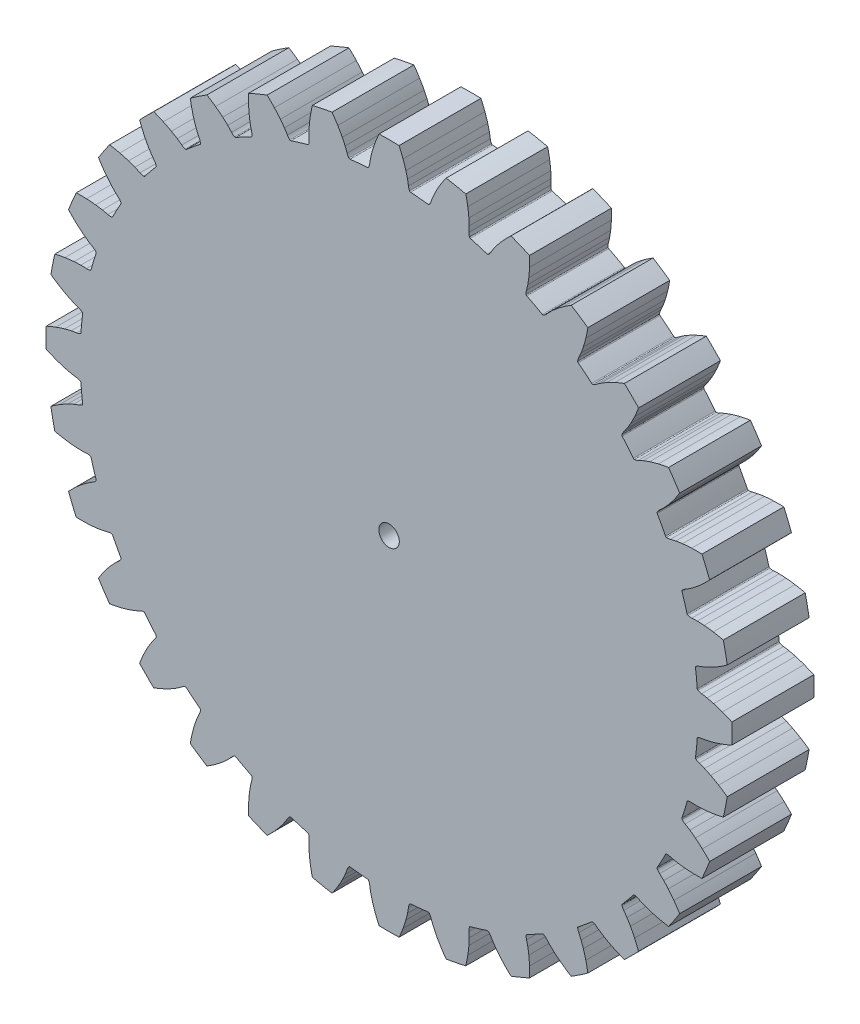
SolidWorks part; units mm, degrees
ref_plane "Front Plane" through (0, 0, 0) normal (0, 0, 1) x (1, 0, 0)
ref_plane "Top Plane" through (0, 0, 0) normal (0, 1, 0) x (1, 0, 0)
ref_plane "Right Plane" through (0, 0, 0) normal (1, 0, 0) x (0, 0, -1)
sketch "Model" plane through (0, 0, 0) normal (0, 0, 1) x (1, 0, 0)
  arc A1 (47.6887, -4.6969) -> (47.803, -3.3385) centre (0, 0) ccw
  arc A2 (47.9144, -3.1714) -> (47.803, -3.3385) centre (48.0052, -3.3526) ccw
  arc A3 (48.4758, -3.0015) -> (47.9144, -3.1714) centre (48.6888, -4.7173) ccw
  arc A4 (48.4758, -3.0015) -> (49.3301, -2.859) centre (47.1969, 7.2969) ccw
  arc A5 (49.3301, -2.859) -> (50.3502, -2.6078) centre (46.1914, 12.0843) ccw
  arc A6 (50.3502, -2.6078) -> (51.6994, -2.1663) centre (45.5635, 14.3022) ccw
  arc A7 (51.6994, -2.1663) -> (53.1817, -1.5528) centre (43.8651, 18.8607) ccw
  arc A8 (53.1817, -1.5528) -> (53.1817, 1.5528) centre (0, 0) ccw
  arc A9 (53.1817, 1.5528) -> (51.6994, 2.1663) centre (43.8651, -18.8607) ccw
  arc A10 (51.6994, 2.1663) -> (50.3502, 2.6078) centre (45.5635, -14.3022) ccw
  arc A11 (50.3502, 2.6078) -> (49.3301, 2.859) centre (46.1914, -12.0843) ccw
  arc A12 (49.3301, 2.859) -> (48.4758, 3.0015) centre (47.1969, -7.2969) ccw
  arc A13 (47.9144, 3.1714) -> (48.4758, 3.0015) centre (48.6888, 4.7173) ccw
  arc A14 (47.803, 3.3385) -> (47.9144, 3.1714) centre (48.0052, 3.3526) ccw
  arc A15 (47.803, 3.3385) -> (47.5358, 6.0515) centre (0, 0) ccw
  arc A16 (47.6124, 6.2371) -> (47.5358, 6.0515) centre (47.7368, 6.0771) ccw
  arc A17 (48.1299, 6.5133) -> (47.6124, 6.2371) centre (48.6736, 4.872) ccw
  arc A18 (48.1299, 6.5133) -> (48.94, 6.8198) centre (44.8665, 16.3643) ccw
  arc A19 (48.94, 6.8198) -> (49.8915, 7.2652) centre (42.9463, 20.8636) ccw
  arc A20 (49.8915, 7.2652) -> (51.1287, 7.9614) centre (41.8978, 22.9164) ccw
  arc A21 (51.1287, 7.9614) -> (52.4627, 8.8522) centre (39.3427, 27.056) ccw
  arc A22 (52.4627, 8.8522) -> (51.8568, 11.8982) centre (0, 0) ccw
  arc A23 (51.8568, 11.8982) -> (50.2834, 12.2107) centre (46.7018, -9.9407) ccw
  arc A24 (50.2834, 12.2107) -> (48.874, 12.3805) centre (47.4783, -5.1384) ccw
  arc A25 (48.874, 12.3805) -> (47.8244, 12.4279) centre (47.6613, -2.8406) ccw
  arc A26 (47.8244, 12.4279) -> (46.9587, 12.401) centre (47.7136, 2.051) ccw
  arc A27 (46.375, 12.4581) -> (46.9587, 12.401) centre (46.833, 14.1254) ccw
  arc A28 (46.2332, 12.6003) -> (46.375, 12.4581) centre (46.4287, 12.6536) ccw
  arc A29 (46.2332, 12.6003) -> (45.4418, 15.209) centre (0, 0) ccw
  arc A30 (45.4808, 15.406) -> (45.4418, 15.209) centre (45.634, 15.2733) ccw
  arc A31 (45.9344, 15.7779) -> (45.4808, 15.406) centre (46.7879, 14.2741) ccw
  arc A32 (45.9344, 15.7779) -> (46.6691, 16.2364) centre (40.8119, 24.8029) ccw
  arc A33 (46.6691, 16.2364) -> (47.5155, 16.8589) centre (38.0508, 28.8411) ccw
  arc A34 (47.5155, 16.8589) -> (48.5931, 17.7832) centre (36.622, 30.6499) ccw
  arc A35 (48.5931, 17.7832) -> (49.7277, 18.9171) centre (33.3084, 34.2115) ccw
  arc A36 (49.7277, 18.9171) -> (48.5392, 21.7864) centre (0, 0) ccw
  arc A37 (48.5392, 21.7864) -> (46.9351, 21.7859) centre (47.7438, -0.6386) ccw
  arc A38 (46.9351, 21.7859) -> (45.5196, 21.6775) centre (47.5684, 4.2229) ccw
  arc A39 (45.5196, 21.6775) -> (44.481, 21.5192) centre (47.2997, 6.5122) ccw
  arc A40 (44.481, 21.5192) -> (43.6371, 21.3239) centre (46.3967, 11.3201) ccw
  arc A41 (43.0535, 21.2661) -> (43.6371, 21.3239) centre (43.1774, 22.9907) ccw
  arc A42 (42.8866, 21.3778) -> (43.0535, 21.2661) centre (43.068, 21.4682) ccw
  arc A43 (42.8866, 21.3778) -> (41.6015, 23.782) centre (0, 0) ccw
  arc A44 (41.6013, 23.9828) -> (41.6015, 23.782) centre (41.7775, 23.8826) ccw
  arc A45 (41.9737, 24.436) -> (41.6013, 23.9828) centre (43.1041, 23.1277) ccw
  arc A46 (41.9737, 24.436) -> (42.6048, 25.0292) centre (35.1889, 32.2883) ccw
  arc A47 (42.6048, 25.0292) -> (43.3135, 25.8048) centre (31.693, 35.7103) ccw
  arc A48 (43.3135, 25.8048) -> (44.19, 26.9215) centre (29.9388, 37.2056) ccw
  arc A49 (44.19, 26.9215) -> (45.0816, 28.255) centre (25.994, 40.0523) ccw
  arc A50 (45.0816, 28.255) -> (43.3562, 30.8373) centre (0, 0) ccw
  arc A51 (43.3562, 30.8373) -> (41.783, 30.5239) centre (46.951, 8.688) ccw
  arc A52 (41.783, 30.5239) -> (40.4159, 30.1414) centre (45.8306, 13.4219) ccw
  arc A53 (40.4159, 30.1414) -> (39.4281, 29.7835) centre (45.1204, 15.6148) ccw
  arc A54 (39.4281, 29.7835) -> (38.6386, 29.4273) centre (43.2967, 20.1541) ccw
  arc A55 (38.0774, 29.2568) -> (38.6386, 29.4273) centre (37.8625, 30.9724) ccw
  arc A56 (37.892, 29.3338) -> (38.0774, 29.2568) centre (38.0522, 29.4579) ccw
  arc A57 (37.892, 29.3338) -> (36.1625, 31.4411) centre (0, 0) ccw
  arc A58 (36.1231, 31.638) -> (36.1625, 31.4411) centre (36.3154, 31.5741) ccw
  arc A59 (36.3999, 32.1552) -> (36.1231, 31.638) centre (37.7639, 31.0925) ccw
  arc A60 (36.3999, 32.1552) -> (36.9032, 32.86) centre (28.2136, 38.5329) ccw
  arc A61 (36.9032, 32.86) -> (37.447, 33.759) centre (24.1173, 41.2071) ccw
  arc A62 (37.447, 33.759) -> (38.0888, 35.0253) centre (22.1051, 42.3315) ccw
  arc A63 (38.0888, 35.0253) -> (38.7031, 36.5071) centre (17.6808, 44.3539) ccw
  arc A64 (38.7031, 36.5071) -> (36.5071, 38.7031) centre (0, 0) ccw
  arc A65 (36.5071, 38.7031) -> (35.0253, 38.0888) centre (44.3539, 17.6808) ccw
  arc A66 (35.0253, 38.0888) -> (33.759, 37.447) centre (42.3315, 22.1051) ccw
  arc A67 (33.759, 37.447) -> (32.86, 36.9032) centre (41.2071, 24.1173) ccw
  arc A68 (32.86, 36.9032) -> (32.1552, 36.3999) centre (38.5329, 28.2136) ccw
  arc A69 (31.638, 36.1231) -> (32.1552, 36.3999) centre (31.0925, 37.7639) ccw
  arc A70 (31.4411, 36.1625) -> (31.638, 36.1231) centre (31.5741, 36.3154) ccw
  arc A71 (31.4411, 36.1625) -> (29.3338, 37.892) centre (0, 0) ccw
  arc A72 (29.2568, 38.0774) -> (29.3338, 37.892) centre (29.4579, 38.0522) ccw
  arc A73 (29.4273, 38.6386) -> (29.2568, 38.0774) centre (30.9724, 37.8625) ccw
  arc A74 (29.4273, 38.6386) -> (29.7835, 39.4281) centre (20.1541, 43.2967) ccw
  arc A75 (29.7835, 39.4281) -> (30.1414, 40.4159) centre (15.6148, 45.1204) ccw
  arc A76 (30.1414, 40.4159) -> (30.5239, 41.783) centre (13.4219, 45.8306) ccw
  arc A77 (30.5239, 41.783) -> (30.8373, 43.3562) centre (8.688, 46.951) ccw
  arc A78 (30.8373, 43.3562) -> (28.255, 45.0816) centre (0, 0) ccw
  arc A79 (28.255, 45.0816) -> (26.9215, 44.19) centre (40.0523, 25.994) ccw
  arc A80 (26.9215, 44.19) -> (25.8048, 43.3135) centre (37.2056, 29.9388) ccw
  arc A81 (25.8048, 43.3135) -> (25.0292, 42.6048) centre (35.7103, 31.693) ccw
  arc A82 (25.0292, 42.6048) -> (24.436, 41.9737) centre (32.2883, 35.1889) ccw
  arc A83 (23.9828, 41.6013) -> (24.436, 41.9737) centre (23.1277, 43.1041) ccw
  arc A84 (23.782, 41.6015) -> (23.9828, 41.6013) centre (23.8826, 41.7775) ccw
  arc A85 (23.782, 41.6015) -> (21.3778, 42.8866) centre (0, 0) ccw
  arc A86 (21.2661, 43.0535) -> (21.3778, 42.8866) centre (21.4682, 43.068) ccw
  arc A87 (21.3239, 43.6371) -> (21.2661, 43.0535) centre (22.9907, 43.1774) ccw
  arc A88 (21.3239, 43.6371) -> (21.5192, 44.481) centre (11.3201, 46.3967) ccw
  arc A89 (21.5192, 44.481) -> (21.6775, 45.5196) centre (6.5122, 47.2997) ccw
  arc A90 (21.6775, 45.5196) -> (21.7859, 46.9351) centre (4.2229, 47.5684) ccw
  arc A91 (21.7859, 46.9351) -> (21.7864, 48.5392) centre (-0.6386, 47.7438) ccw
  arc A92 (21.7864, 48.5392) -> (18.9171, 49.7277) centre (0, 0) ccw
  arc A93 (18.9171, 49.7277) -> (17.7832, 48.5931) centre (34.2115, 33.3084) ccw
  arc A94 (17.7832, 48.5931) -> (16.8589, 47.5155) centre (30.6499, 36.622) ccw
  arc A95 (16.8589, 47.5155) -> (16.2364, 46.6691) centre (28.8411, 38.0508) ccw
  arc A96 (16.2364, 46.6691) -> (15.7779, 45.9344) centre (24.8029, 40.8119) ccw
  arc A97 (15.406, 45.4808) -> (15.7779, 45.9344) centre (14.2741, 46.7879) ccw
  arc A98 (15.209, 45.4418) -> (15.406, 45.4808) centre (15.2733, 45.634) ccw
  arc A99 (15.209, 45.4418) -> (12.6003, 46.2332) centre (0, 0) ccw
  arc A100 (12.4581, 46.375) -> (12.6003, 46.2332) centre (12.6536, 46.4287) ccw
  arc A101 (12.401, 46.9587) -> (12.4581, 46.375) centre (14.1254, 46.833) ccw
  arc A102 (12.401, 46.9587) -> (12.4279, 47.8244) centre (2.051, 47.7136) ccw
  arc A103 (12.4279, 47.8244) -> (12.3805, 48.874) centre (-2.8406, 47.6613) ccw
  arc A104 (12.3805, 48.874) -> (12.2107, 50.2834) centre (-5.1384, 47.4783) ccw
  arc A105 (12.2107, 50.2834) -> (11.8982, 51.8568) centre (-9.9407, 46.7018) ccw
  arc A106 (11.8982, 51.8568) -> (8.8522, 52.4627) centre (0, 0) ccw
  arc A107 (8.8522, 52.4627) -> (7.9614, 51.1287) centre (27.056, 39.3427) ccw
  arc A108 (7.9614, 51.1287) -> (7.2652, 49.8915) centre (22.9164, 41.8978) ccw
  arc A109 (7.2652, 49.8915) -> (6.8198, 48.94) centre (20.8636, 42.9463) ccw
  arc A110 (6.8198, 48.94) -> (6.5133, 48.1299) centre (16.3643, 44.8665) ccw
  arc A111 (6.2371, 47.6124) -> (6.5133, 48.1299) centre (4.872, 48.6736) ccw
  arc A112 (6.0515, 47.5358) -> (6.2371, 47.6124) centre (6.0771, 47.7368) ccw
  arc A113 (6.0515, 47.5358) -> (3.3385, 47.803) centre (0, 0) ccw
  arc A114 (3.1714, 47.9144) -> (3.3385, 47.803) centre (3.3526, 48.0052) ccw
  arc A115 (3.0015, 48.4758) -> (3.1714, 47.9144) centre (4.7173, 48.6888) ccw
  arc A116 (3.0015, 48.4758) -> (2.859, 49.3301) centre (-7.2969, 47.1969) ccw
  arc A117 (2.859, 49.3301) -> (2.6078, 50.3502) centre (-12.0843, 46.1914) ccw
  arc A118 (2.6078, 50.3502) -> (2.1663, 51.6994) centre (-14.3022, 45.5635) ccw
  arc A119 (2.1663, 51.6994) -> (1.5528, 53.1817) centre (-18.8607, 43.8651) ccw
  arc A120 (1.5528, 53.1817) -> (-1.5528, 53.1817) centre (0, 0) ccw
  arc A121 (-1.5528, 53.1817) -> (-2.1663, 51.6994) centre (18.8607, 43.8651) ccw
  arc A122 (-2.1663, 51.6994) -> (-2.6078, 50.3502) centre (14.3022, 45.5635) ccw
  arc A123 (-2.6078, 50.3502) -> (-2.859, 49.3301) centre (12.0843, 46.1914) ccw
  arc A124 (-2.859, 49.3301) -> (-3.0015, 48.4758) centre (7.2969, 47.1969) ccw
  arc A125 (-3.1714, 47.9144) -> (-3.0015, 48.4758) centre (-4.7173, 48.6888) ccw
  arc A126 (-3.3385, 47.803) -> (-3.1714, 47.9144) centre (-3.3526, 48.0052) ccw
  arc A127 (-3.3385, 47.803) -> (-6.0515, 47.5358) centre (0, 0) ccw
  arc A128 (-6.2371, 47.6124) -> (-6.0515, 47.5358) centre (-6.0771, 47.7368) ccw
  arc A129 (-6.5133, 48.1299) -> (-6.2371, 47.6124) centre (-4.872, 48.6736) ccw
  arc A130 (-6.5133, 48.1299) -> (-6.8198, 48.94) centre (-16.3643, 44.8665) ccw
  arc A131 (-6.8198, 48.94) -> (-7.2652, 49.8915) centre (-20.8636, 42.9463) ccw
  arc A132 (-7.2652, 49.8915) -> (-7.9614, 51.1287) centre (-22.9164, 41.8978) ccw
  arc A133 (-7.9614, 51.1287) -> (-8.8522, 52.4627) centre (-27.056, 39.3427) ccw
  arc A134 (-8.8522, 52.4627) -> (-11.8982, 51.8568) centre (0, 0) ccw
  arc A135 (-11.8982, 51.8568) -> (-12.2107, 50.2834) centre (9.9407, 46.7018) ccw
  arc A136 (-12.2107, 50.2834) -> (-12.3805, 48.874) centre (5.1384, 47.4783) ccw
  arc A137 (-12.3805, 48.874) -> (-12.4279, 47.8244) centre (2.8406, 47.6613) ccw
  arc A138 (-12.4279, 47.8244) -> (-12.401, 46.9587) centre (-2.051, 47.7136) ccw
  arc A139 (-12.4581, 46.375) -> (-12.401, 46.9587) centre (-14.1254, 46.833) ccw
  arc A140 (-12.6003, 46.2332) -> (-12.4581, 46.375) centre (-12.6536, 46.4287) ccw
  arc A141 (-12.6003, 46.2332) -> (-15.209, 45.4418) centre (0, 0) ccw
  arc A142 (-15.406, 45.4808) -> (-15.209, 45.4418) centre (-15.2733, 45.634) ccw
  arc A143 (-15.7779, 45.9344) -> (-15.406, 45.4808) centre (-14.2741, 46.7879) ccw
  arc A144 (-15.7779, 45.9344) -> (-16.2364, 46.6691) centre (-24.8029, 40.8119) ccw
  arc A145 (-16.2364, 46.6691) -> (-16.8589, 47.5155) centre (-28.8411, 38.0508) ccw
  arc A146 (-16.8589, 47.5155) -> (-17.7832, 48.5931) centre (-30.6499, 36.622) ccw
  arc A147 (-17.7832, 48.5931) -> (-18.9171, 49.7277) centre (-34.2115, 33.3084) ccw
  arc A148 (-18.9171, 49.7277) -> (-21.7864, 48.5392) centre (0, 0) ccw
  arc A149 (-21.7864, 48.5392) -> (-21.7859, 46.9351) centre (0.6386, 47.7438) ccw
  arc A150 (-21.7859, 46.9351) -> (-21.6775, 45.5196) centre (-4.2229, 47.5684) ccw
  arc A151 (-21.6775, 45.5196) -> (-21.5192, 44.481) centre (-6.5122, 47.2997) ccw
  arc A152 (-21.5192, 44.481) -> (-21.3239, 43.6371) centre (-11.3201, 46.3967) ccw
  arc A153 (-21.2661, 43.0535) -> (-21.3239, 43.6371) centre (-22.9907, 43.1774) ccw
  arc A154 (-21.3778, 42.8866) -> (-21.2661, 43.0535) centre (-21.4682, 43.068) ccw
  arc A155 (-21.3778, 42.8866) -> (-23.782, 41.6015) centre (0, 0) ccw
  arc A156 (-23.9828, 41.6013) -> (-23.782, 41.6015) centre (-23.8826, 41.7775) ccw
  arc A157 (-24.436, 41.9737) -> (-23.9828, 41.6013) centre (-23.1277, 43.1041) ccw
  arc A158 (-24.436, 41.9737) -> (-25.0292, 42.6048) centre (-32.2883, 35.1889) ccw
  arc A159 (-25.0292, 42.6048) -> (-25.8048, 43.3135) centre (-35.7103, 31.693) ccw
  arc A160 (-25.8048, 43.3135) -> (-26.9215, 44.19) centre (-37.2056, 29.9388) ccw
  arc A161 (-26.9215, 44.19) -> (-28.255, 45.0816) centre (-40.0523, 25.994) ccw
  arc A162 (-28.255, 45.0816) -> (-30.8373, 43.3562) centre (0, 0) ccw
  arc A163 (-30.8373, 43.3562) -> (-30.5239, 41.783) centre (-8.688, 46.951) ccw
  arc A164 (-30.5239, 41.783) -> (-30.1414, 40.4159) centre (-13.4219, 45.8306) ccw
  arc A165 (-30.1414, 40.4159) -> (-29.7835, 39.4281) centre (-15.6148, 45.1204) ccw
  arc A166 (-29.7835, 39.4281) -> (-29.4273, 38.6386) centre (-20.1541, 43.2967) ccw
  arc A167 (-29.2568, 38.0774) -> (-29.4273, 38.6386) centre (-30.9724, 37.8625) ccw
  arc A168 (-29.3338, 37.892) -> (-29.2568, 38.0774) centre (-29.4579, 38.0522) ccw
  arc A169 (-29.3338, 37.892) -> (-31.4411, 36.1625) centre (0, 0) ccw
  arc A170 (-31.638, 36.1231) -> (-31.4411, 36.1625) centre (-31.5741, 36.3154) ccw
  arc A171 (-32.1552, 36.3999) -> (-31.638, 36.1231) centre (-31.0925, 37.7639) ccw
  arc A172 (-32.1552, 36.3999) -> (-32.86, 36.9032) centre (-38.5329, 28.2136) ccw
  arc A173 (-32.86, 36.9032) -> (-33.759, 37.447) centre (-41.2071, 24.1173) ccw
  arc A174 (-33.759, 37.447) -> (-35.0253, 38.0888) centre (-42.3315, 22.1051) ccw
  arc A175 (-35.0253, 38.0888) -> (-36.5071, 38.7031) centre (-44.3539, 17.6808) ccw
  arc A176 (-36.5071, 38.7031) -> (-38.7031, 36.5071) centre (0, 0) ccw
  arc A177 (-38.7031, 36.5071) -> (-38.0888, 35.0253) centre (-17.6808, 44.3539) ccw
  arc A178 (-38.0888, 35.0253) -> (-37.447, 33.759) centre (-22.1051, 42.3315) ccw
  arc A179 (-37.447, 33.759) -> (-36.9032, 32.86) centre (-24.1173, 41.2071) ccw
  arc A180 (-36.9032, 32.86) -> (-36.3999, 32.1552) centre (-28.2136, 38.5329) ccw
  arc A181 (-36.1231, 31.638) -> (-36.3999, 32.1552) centre (-37.7639, 31.0925) ccw
  arc A182 (-36.1625, 31.4411) -> (-36.1231, 31.638) centre (-36.3154, 31.5741) ccw
  arc A183 (-36.1625, 31.4411) -> (-37.892, 29.3338) centre (0, 0) ccw
  arc A184 (-38.0774, 29.2568) -> (-37.892, 29.3338) centre (-38.0522, 29.4579) ccw
  arc A185 (-38.6386, 29.4273) -> (-38.0774, 29.2568) centre (-37.8625, 30.9724) ccw
  arc A186 (-38.6386, 29.4273) -> (-39.4281, 29.7835) centre (-43.2967, 20.1541) ccw
  arc A187 (-39.4281, 29.7835) -> (-40.4159, 30.1414) centre (-45.1204, 15.6148) ccw
  arc A188 (-40.4159, 30.1414) -> (-41.783, 30.5239) centre (-45.8306, 13.4219) ccw
  arc A189 (-41.783, 30.5239) -> (-43.3562, 30.8373) centre (-46.951, 8.688) ccw
  arc A190 (-43.3562, 30.8373) -> (-45.0816, 28.255) centre (0, 0) ccw
  arc A191 (-45.0816, 28.255) -> (-44.19, 26.9215) centre (-25.994, 40.0523) ccw
  arc A192 (-44.19, 26.9215) -> (-43.3135, 25.8048) centre (-29.9388, 37.2056) ccw
  arc A193 (-43.3135, 25.8048) -> (-42.6048, 25.0292) centre (-31.693, 35.7103) ccw
  arc A194 (-42.6048, 25.0292) -> (-41.9737, 24.436) centre (-35.1889, 32.2883) ccw
  arc A195 (-41.6013, 23.9828) -> (-41.9737, 24.436) centre (-43.1041, 23.1277) ccw
  arc A196 (-41.6015, 23.782) -> (-41.6013, 23.9828) centre (-41.7775, 23.8826) ccw
  arc A197 (-41.6015, 23.782) -> (-42.8866, 21.3778) centre (0, 0) ccw
  arc A198 (-43.0535, 21.2661) -> (-42.8866, 21.3778) centre (-43.068, 21.4682) ccw
  arc A199 (-43.6371, 21.3239) -> (-43.0535, 21.2661) centre (-43.1774, 22.9907) ccw
  arc A200 (-43.6371, 21.3239) -> (-44.481, 21.5192) centre (-46.3967, 11.3201) ccw
  arc A201 (-44.481, 21.5192) -> (-45.5196, 21.6775) centre (-47.2997, 6.5122) ccw
  arc A202 (-45.5196, 21.6775) -> (-46.9351, 21.7859) centre (-47.5684, 4.2229) ccw
  arc A203 (-46.9351, 21.7859) -> (-48.5392, 21.7864) centre (-47.7438, -0.6386) ccw
  arc A204 (-48.5392, 21.7864) -> (-49.7277, 18.9171) centre (0, 0) ccw
  arc A205 (-49.7277, 18.9171) -> (-48.5931, 17.7832) centre (-33.3084, 34.2115) ccw
  arc A206 (-48.5931, 17.7832) -> (-47.5155, 16.8589) centre (-36.622, 30.6499) ccw
  arc A207 (-47.5155, 16.8589) -> (-46.6691, 16.2364) centre (-38.0508, 28.8411) ccw
  arc A208 (-46.6691, 16.2364) -> (-45.9344, 15.7779) centre (-40.8119, 24.8029) ccw
  arc A209 (-45.4808, 15.406) -> (-45.9344, 15.7779) centre (-46.7879, 14.2741) ccw
  arc A210 (-45.4418, 15.209) -> (-45.4808, 15.406) centre (-45.634, 15.2733) ccw
  arc A211 (-45.4418, 15.209) -> (-46.2332, 12.6003) centre (0, 0) ccw
  arc A212 (-46.375, 12.4581) -> (-46.2332, 12.6003) centre (-46.4287, 12.6536) ccw
  arc A213 (-46.9587, 12.401) -> (-46.375, 12.4581) centre (-46.833, 14.1254) ccw
  arc A214 (-46.9587, 12.401) -> (-47.8244, 12.4279) centre (-47.7136, 2.051) ccw
  arc A215 (-47.8244, 12.4279) -> (-48.874, 12.3805) centre (-47.6613, -2.8406) ccw
  arc A216 (-48.874, 12.3805) -> (-50.2834, 12.2107) centre (-47.4783, -5.1384) ccw
  arc A217 (-50.2834, 12.2107) -> (-51.8568, 11.8982) centre (-46.7018, -9.9407) ccw
  arc A218 (-51.8568, 11.8982) -> (-52.4627, 8.8522) centre (0, 0) ccw
  arc A219 (-52.4627, 8.8522) -> (-51.1287, 7.9614) centre (-39.3427, 27.056) ccw
  arc A220 (-51.1287, 7.9614) -> (-49.8915, 7.2652) centre (-41.8978, 22.9164) ccw
  arc A221 (-49.8915, 7.2652) -> (-48.94, 6.8198) centre (-42.9463, 20.8636) ccw
  arc A222 (-48.94, 6.8198) -> (-48.1299, 6.5133) centre (-44.8665, 16.3643) ccw
  arc A223 (-47.6124, 6.2371) -> (-48.1299, 6.5133) centre (-48.6736, 4.872) ccw
  arc A224 (-47.5358, 6.0515) -> (-47.6124, 6.2371) centre (-47.7368, 6.0771) ccw
  arc A225 (-47.5358, 6.0515) -> (-47.803, 3.3385) centre (0, 0) ccw
  arc A226 (-47.9144, 3.1714) -> (-47.803, 3.3385) centre (-48.0052, 3.3526) ccw
  arc A227 (-48.4758, 3.0015) -> (-47.9144, 3.1714) centre (-48.6888, 4.7173) ccw
  arc A228 (-48.4758, 3.0015) -> (-49.3301, 2.859) centre (-47.1969, -7.2969) ccw
  arc A229 (-49.3301, 2.859) -> (-50.3502, 2.6078) centre (-46.1914, -12.0843) ccw
  arc A230 (-50.3502, 2.6078) -> (-51.6994, 2.1663) centre (-45.5635, -14.3022) ccw
  arc A231 (-51.6994, 2.1663) -> (-53.1817, 1.5528) centre (-43.8651, -18.8607) ccw
  arc A232 (-53.1817, 1.5528) -> (-53.1817, -1.5528) centre (0, 0) ccw
  arc A233 (-53.1817, -1.5528) -> (-51.6994, -2.1663) centre (-43.8651, 18.8607) ccw
  arc A234 (-51.6994, -2.1663) -> (-50.3502, -2.6078) centre (-45.5635, 14.3022) ccw
  arc A235 (-50.3502, -2.6078) -> (-49.3301, -2.859) centre (-46.1914, 12.0843) ccw
  arc A236 (-49.3301, -2.859) -> (-48.4758, -3.0015) centre (-47.1969, 7.2969) ccw
  arc A237 (-47.9144, -3.1714) -> (-48.4758, -3.0015) centre (-48.6888, -4.7173) ccw
  arc A238 (-47.803, -3.3385) -> (-47.9144, -3.1714) centre (-48.0052, -3.3526) ccw
  arc A239 (-47.803, -3.3385) -> (-47.5358, -6.0515) centre (0, 0) ccw
  arc A240 (-47.6124, -6.2371) -> (-47.5358, -6.0515) centre (-47.7368, -6.0771) ccw
  arc A241 (-48.1299, -6.5133) -> (-47.6124, -6.2371) centre (-48.6736, -4.872) ccw
  arc A242 (-48.1299, -6.5133) -> (-48.94, -6.8198) centre (-44.8665, -16.3643) ccw
  arc A243 (-48.94, -6.8198) -> (-49.8915, -7.2652) centre (-42.9463, -20.8636) ccw
  arc A244 (-49.8915, -7.2652) -> (-51.1287, -7.9614) centre (-41.8978, -22.9164) ccw
  arc A245 (-51.1287, -7.9614) -> (-52.4627, -8.8522) centre (-39.3427, -27.056) ccw
  arc A246 (-52.4627, -8.8522) -> (-51.8568, -11.8982) centre (0, 0) ccw
  arc A247 (-51.8568, -11.8982) -> (-50.2834, -12.2107) centre (-46.7018, 9.9407) ccw
  arc A248 (-50.2834, -12.2107) -> (-48.874, -12.3805) centre (-47.4783, 5.1384) ccw
  arc A249 (-48.874, -12.3805) -> (-47.8244, -12.4279) centre (-47.6613, 2.8406) ccw
  arc A250 (-47.8244, -12.4279) -> (-46.9587, -12.401) centre (-47.7136, -2.051) ccw
  arc A251 (-46.375, -12.4581) -> (-46.9587, -12.401) centre (-46.833, -14.1254) ccw
  arc A252 (-46.2332, -12.6003) -> (-46.375, -12.4581) centre (-46.4287, -12.6536) ccw
  arc A253 (-46.2332, -12.6003) -> (-45.4418, -15.209) centre (0, 0) ccw
  arc A254 (-45.4808, -15.406) -> (-45.4418, -15.209) centre (-45.634, -15.2733) ccw
  arc A255 (-45.9344, -15.7779) -> (-45.4808, -15.406) centre (-46.7879, -14.2741) ccw
  arc A256 (-45.9344, -15.7779) -> (-46.6691, -16.2364) centre (-40.8119, -24.8029) ccw
  arc A257 (-46.6691, -16.2364) -> (-47.5155, -16.8589) centre (-38.0508, -28.8411) ccw
  arc A258 (-47.5155, -16.8589) -> (-48.5931, -17.7832) centre (-36.622, -30.6499) ccw
  arc A259 (-48.5931, -17.7832) -> (-49.7277, -18.9171) centre (-33.3084, -34.2115) ccw
  arc A260 (-49.7277, -18.9171) -> (-48.5392, -21.7864) centre (0, 0) ccw
  arc A261 (-48.5392, -21.7864) -> (-46.9351, -21.7859) centre (-47.7438, 0.6386) ccw
  arc A262 (-46.9351, -21.7859) -> (-45.5196, -21.6775) centre (-47.5684, -4.2229) ccw
  arc A263 (-45.5196, -21.6775) -> (-44.481, -21.5192) centre (-47.2997, -6.5122) ccw
  arc A264 (-44.481, -21.5192) -> (-43.6371, -21.3239) centre (-46.3967, -11.3201) ccw
  arc A265 (-43.0535, -21.2661) -> (-43.6371, -21.3239) centre (-43.1774, -22.9907) ccw
  arc A266 (-42.8866, -21.3778) -> (-43.0535, -21.2661) centre (-43.068, -21.4682) ccw
  arc A267 (-42.8866, -21.3778) -> (-41.6015, -23.782) centre (0, 0) ccw
  arc A268 (-41.6013, -23.9828) -> (-41.6015, -23.782) centre (-41.7775, -23.8826) ccw
  arc A269 (-41.9737, -24.436) -> (-41.6013, -23.9828) centre (-43.1041, -23.1277) ccw
  arc A270 (-41.9737, -24.436) -> (-42.6048, -25.0292) centre (-35.1889, -32.2883) ccw
  arc A271 (-42.6048, -25.0292) -> (-43.3135, -25.8048) centre (-31.693, -35.7103) ccw
  arc A272 (-43.3135, -25.8048) -> (-44.19, -26.9215) centre (-29.9388, -37.2056) ccw
  arc A273 (-44.19, -26.9215) -> (-45.0816, -28.255) centre (-25.994, -40.0523) ccw
  arc A274 (-45.0816, -28.255) -> (-43.3562, -30.8373) centre (0, 0) ccw
  arc A275 (-43.3562, -30.8373) -> (-41.783, -30.5239) centre (-46.951, -8.688) ccw
  arc A276 (-41.783, -30.5239) -> (-40.4159, -30.1414) centre (-45.8306, -13.4219) ccw
  arc A277 (-40.4159, -30.1414) -> (-39.4281, -29.7835) centre (-45.1204, -15.6148) ccw
  arc A278 (-39.4281, -29.7835) -> (-38.6386, -29.4273) centre (-43.2967, -20.1541) ccw
  arc A279 (-38.0774, -29.2568) -> (-38.6386, -29.4273) centre (-37.8625, -30.9724) ccw
  arc A280 (-37.892, -29.3338) -> (-38.0774, -29.2568) centre (-38.0522, -29.4579) ccw
  arc A281 (-37.892, -29.3338) -> (-36.1625, -31.4411) centre (0, 0) ccw
  arc A282 (-36.1231, -31.638) -> (-36.1625, -31.4411) centre (-36.3154, -31.5741) ccw
  arc A283 (-36.3999, -32.1552) -> (-36.1231, -31.638) centre (-37.7639, -31.0925) ccw
  arc A284 (-36.3999, -32.1552) -> (-36.9032, -32.86) centre (-28.2136, -38.5329) ccw
  arc A285 (-36.9032, -32.86) -> (-37.447, -33.759) centre (-24.1173, -41.2071) ccw
  arc A286 (-37.447, -33.759) -> (-38.0888, -35.0253) centre (-22.1051, -42.3315) ccw
  arc A287 (-38.0888, -35.0253) -> (-38.7031, -36.5071) centre (-17.6808, -44.3539) ccw
  arc A288 (-38.7031, -36.5071) -> (-36.5071, -38.7031) centre (0, 0) ccw
  arc A289 (-36.5071, -38.7031) -> (-35.0253, -38.0888) centre (-44.3539, -17.6808) ccw
  arc A290 (-35.0253, -38.0888) -> (-33.759, -37.447) centre (-42.3315, -22.1051) ccw
  arc A291 (-33.759, -37.447) -> (-32.86, -36.9032) centre (-41.2071, -24.1173) ccw
  arc A292 (-32.86, -36.9032) -> (-32.1552, -36.3999) centre (-38.5329, -28.2136) ccw
  arc A293 (-31.638, -36.1231) -> (-32.1552, -36.3999) centre (-31.0925, -37.7639) ccw
  arc A294 (-31.4411, -36.1625) -> (-31.638, -36.1231) centre (-31.5741, -36.3154) ccw
  arc A295 (-31.4411, -36.1625) -> (-29.3338, -37.892) centre (0, 0) ccw
  arc A296 (-29.2568, -38.0774) -> (-29.3338, -37.892) centre (-29.4579, -38.0522) ccw
  arc A297 (-29.4273, -38.6386) -> (-29.2568, -38.0774) centre (-30.9724, -37.8625) ccw
  arc A298 (-29.4273, -38.6386) -> (-29.7835, -39.4281) centre (-20.1541, -43.2967) ccw
  arc A299 (-29.7835, -39.4281) -> (-30.1414, -40.4159) centre (-15.6148, -45.1204) ccw
  arc A300 (-30.1414, -40.4159) -> (-30.5239, -41.783) centre (-13.4219, -45.8306) ccw
  arc A301 (-30.5239, -41.783) -> (-30.8373, -43.3562) centre (-8.688, -46.951) ccw
  arc A302 (-30.8373, -43.3562) -> (-28.255, -45.0816) centre (0, 0) ccw
  arc A303 (-28.255, -45.0816) -> (-26.9215, -44.19) centre (-40.0523, -25.994) ccw
  arc A304 (-26.9215, -44.19) -> (-25.8048, -43.3135) centre (-37.2056, -29.9388) ccw
  arc A305 (-25.8048, -43.3135) -> (-25.0292, -42.6048) centre (-35.7103, -31.693) ccw
  arc A306 (-25.0292, -42.6048) -> (-24.436, -41.9737) centre (-32.2883, -35.1889) ccw
  arc A307 (-23.9828, -41.6013) -> (-24.436, -41.9737) centre (-23.1277, -43.1041) ccw
  arc A308 (-23.782, -41.6015) -> (-23.9828, -41.6013) centre (-23.8826, -41.7775) ccw
  arc A309 (-23.782, -41.6015) -> (-21.3778, -42.8866) centre (0, 0) ccw
  arc A310 (-21.2661, -43.0535) -> (-21.3778, -42.8866) centre (-21.4682, -43.068) ccw
  arc A311 (-21.3239, -43.6371) -> (-21.2661, -43.0535) centre (-22.9907, -43.1774) ccw
  arc A312 (-21.3239, -43.6371) -> (-21.5192, -44.481) centre (-11.3201, -46.3967) ccw
  arc A313 (-21.5192, -44.481) -> (-21.6775, -45.5196) centre (-6.5122, -47.2997) ccw
  arc A314 (-21.6775, -45.5196) -> (-21.7859, -46.9351) centre (-4.2229, -47.5684) ccw
  arc A315 (-21.7859, -46.9351) -> (-21.7864, -48.5392) centre (0.6386, -47.7438) ccw
  arc A316 (-21.7864, -48.5392) -> (-18.9171, -49.7277) centre (0, 0) ccw
  arc A317 (-18.9171, -49.7277) -> (-17.7832, -48.5931) centre (-34.2115, -33.3084) ccw
  arc A318 (-17.7832, -48.5931) -> (-16.8589, -47.5155) centre (-30.6499, -36.622) ccw
  arc A319 (-16.8589, -47.5155) -> (-16.2364, -46.6691) centre (-28.8411, -38.0508) ccw
  arc A320 (-16.2364, -46.6691) -> (-15.7779, -45.9344) centre (-24.8029, -40.8119) ccw
  arc A321 (-15.406, -45.4808) -> (-15.7779, -45.9344) centre (-14.2741, -46.7879) ccw
  arc A322 (-15.209, -45.4418) -> (-15.406, -45.4808) centre (-15.2733, -45.634) ccw
  arc A323 (-15.209, -45.4418) -> (-12.6003, -46.2332) centre (0, 0) ccw
  arc A324 (-12.4581, -46.375) -> (-12.6003, -46.2332) centre (-12.6536, -46.4287) ccw
  arc A325 (-12.401, -46.9587) -> (-12.4581, -46.375) centre (-14.1254, -46.833) ccw
  arc A326 (-12.401, -46.9587) -> (-12.4279, -47.8244) centre (-2.051, -47.7136) ccw
  arc A327 (-12.4279, -47.8244) -> (-12.3805, -48.874) centre (2.8406, -47.6613) ccw
  arc A328 (-12.3805, -48.874) -> (-12.2107, -50.2834) centre (5.1384, -47.4783) ccw
  arc A329 (-12.2107, -50.2834) -> (-11.8982, -51.8568) centre (9.9407, -46.7018) ccw
  arc A330 (-11.8982, -51.8568) -> (-8.8522, -52.4627) centre (0, 0) ccw
  arc A331 (-8.8522, -52.4627) -> (-7.9614, -51.1287) centre (-27.056, -39.3427) ccw
  arc A332 (-7.9614, -51.1287) -> (-7.2652, -49.8915) centre (-22.9164, -41.8978) ccw
  arc A333 (-7.2652, -49.8915) -> (-6.8198, -48.94) centre (-20.8636, -42.9463) ccw
  arc A334 (-6.8198, -48.94) -> (-6.5133, -48.1299) centre (-16.3643, -44.8665) ccw
  arc A335 (-6.2371, -47.6124) -> (-6.5133, -48.1299) centre (-4.872, -48.6736) ccw
  arc A336 (-6.0515, -47.5358) -> (-6.2371, -47.6124) centre (-6.0771, -47.7368) ccw
  arc A337 (-6.0515, -47.5358) -> (-3.3385, -47.803) centre (0, 0) ccw
  arc A338 (-3.1714, -47.9144) -> (-3.3385, -47.803) centre (-3.3526, -48.0052) ccw
  arc A339 (-3.0015, -48.4758) -> (-3.1714, -47.9144) centre (-4.7173, -48.6888) ccw
  arc A340 (-3.0015, -48.4758) -> (-2.859, -49.3301) centre (7.2969, -47.1969) ccw
  arc A341 (-2.859, -49.3301) -> (-2.6078, -50.3502) centre (12.0843, -46.1914) ccw
  arc A342 (-2.6078, -50.3502) -> (-2.1663, -51.6994) centre (14.3022, -45.5635) ccw
  arc A343 (-2.1663, -51.6994) -> (-1.5528, -53.1817) centre (18.8607, -43.8651) ccw
  arc A344 (-1.5528, -53.1817) -> (1.5528, -53.1817) centre (0, 0) ccw
  arc A345 (1.5528, -53.1817) -> (2.1663, -51.6994) centre (-18.8607, -43.8651) ccw
  arc A346 (2.1663, -51.6994) -> (2.6078, -50.3502) centre (-14.3022, -45.5635) ccw
  arc A347 (2.6078, -50.3502) -> (2.859, -49.3301) centre (-12.0843, -46.1914) ccw
  arc A348 (2.859, -49.3301) -> (3.0015, -48.4758) centre (-7.2969, -47.1969) ccw
  arc A349 (3.1714, -47.9144) -> (3.0015, -48.4758) centre (4.7173, -48.6888) ccw
  arc A350 (3.3385, -47.803) -> (3.1714, -47.9144) centre (3.3526, -48.0052) ccw
  arc A351 (3.3385, -47.803) -> (6.0515, -47.5358) centre (0, 0) ccw
  arc A352 (6.2371, -47.6124) -> (6.0515, -47.5358) centre (6.0771, -47.7368) ccw
  arc A353 (6.5133, -48.1299) -> (6.2371, -47.6124) centre (4.872, -48.6736) ccw
  arc A354 (6.5133, -48.1299) -> (6.8198, -48.94) centre (16.3643, -44.8665) ccw
  arc A355 (6.8198, -48.94) -> (7.2652, -49.8915) centre (20.8636, -42.9463) ccw
  arc A356 (7.2652, -49.8915) -> (7.9614, -51.1287) centre (22.9164, -41.8978) ccw
  arc A357 (7.9614, -51.1287) -> (8.8522, -52.4627) centre (27.056, -39.3427) ccw
  arc A358 (8.8522, -52.4627) -> (11.8982, -51.8568) centre (0, 0) ccw
  arc A359 (11.8982, -51.8568) -> (12.2107, -50.2834) centre (-9.9407, -46.7018) ccw
  arc A360 (12.2107, -50.2834) -> (12.3805, -48.874) centre (-5.1384, -47.4783) ccw
  arc A361 (12.3805, -48.874) -> (12.4279, -47.8244) centre (-2.8406, -47.6613) ccw
  arc A362 (12.4279, -47.8244) -> (12.401, -46.9587) centre (2.051, -47.7136) ccw
  arc A363 (12.4581, -46.375) -> (12.401, -46.9587) centre (14.1254, -46.833) ccw
  arc A364 (12.6003, -46.2332) -> (12.4581, -46.375) centre (12.6536, -46.4287) ccw
  arc A365 (12.6003, -46.2332) -> (15.209, -45.4418) centre (0, 0) ccw
  arc A366 (15.406, -45.4808) -> (15.209, -45.4418) centre (15.2733, -45.634) ccw
  arc A367 (15.7779, -45.9344) -> (15.406, -45.4808) centre (14.2741, -46.7879) ccw
  arc A368 (15.7779, -45.9344) -> (16.2364, -46.6691) centre (24.8029, -40.8119) ccw
  arc A369 (16.2364, -46.6691) -> (16.8589, -47.5155) centre (28.8411, -38.0508) ccw
  arc A370 (16.8589, -47.5155) -> (17.7832, -48.5931) centre (30.6499, -36.622) ccw
  arc A371 (17.7832, -48.5931) -> (18.9171, -49.7277) centre (34.2115, -33.3084) ccw
  arc A372 (18.9171, -49.7277) -> (21.7864, -48.5392) centre (0, 0) ccw
  arc A373 (21.7864, -48.5392) -> (21.7859, -46.9351) centre (-0.6386, -47.7438) ccw
  arc A374 (21.7859, -46.9351) -> (21.6775, -45.5196) centre (4.2229, -47.5684) ccw
  arc A375 (21.6775, -45.5196) -> (21.5192, -44.481) centre (6.5122, -47.2997) ccw
  arc A376 (21.5192, -44.481) -> (21.3239, -43.6371) centre (11.3201, -46.3967) ccw
  arc A377 (21.2661, -43.0535) -> (21.3239, -43.6371) centre (22.9907, -43.1774) ccw
  arc A378 (21.3778, -42.8866) -> (21.2661, -43.0535) centre (21.4682, -43.068) ccw
  arc A379 (21.3778, -42.8866) -> (23.782, -41.6015) centre (0, 0) ccw
  arc A380 (23.9828, -41.6013) -> (23.782, -41.6015) centre (23.8826, -41.7775) ccw
  arc A381 (24.436, -41.9737) -> (23.9828, -41.6013) centre (23.1277, -43.1041) ccw
  arc A382 (24.436, -41.9737) -> (25.0292, -42.6048) centre (32.2883, -35.1889) ccw
  arc A383 (25.0292, -42.6048) -> (25.8048, -43.3135) centre (35.7103, -31.693) ccw
  arc A384 (25.8048, -43.3135) -> (26.9215, -44.19) centre (37.2056, -29.9388) ccw
  arc A385 (26.9215, -44.19) -> (28.255, -45.0816) centre (40.0523, -25.994) ccw
  arc A386 (28.255, -45.0816) -> (30.8373, -43.3562) centre (0, 0) ccw
  arc A387 (30.8373, -43.3562) -> (30.5239, -41.783) centre (8.688, -46.951) ccw
  arc A388 (30.5239, -41.783) -> (30.1414, -40.4159) centre (13.4219, -45.8306) ccw
  arc A389 (30.1414, -40.4159) -> (29.7835, -39.4281) centre (15.6148, -45.1204) ccw
  arc A390 (29.7835, -39.4281) -> (29.4273, -38.6386) centre (20.1541, -43.2967) ccw
  arc A391 (29.2568, -38.0774) -> (29.4273, -38.6386) centre (30.9724, -37.8625) ccw
  arc A392 (29.3338, -37.892) -> (29.2568, -38.0774) centre (29.4579, -38.0522) ccw
  arc A393 (29.3338, -37.892) -> (31.4411, -36.1625) centre (0, 0) ccw
  arc A394 (31.638, -36.1231) -> (31.4411, -36.1625) centre (31.5741, -36.3154) ccw
  arc A395 (32.1552, -36.3999) -> (31.638, -36.1231) centre (31.0925, -37.7639) ccw
  arc A396 (32.1552, -36.3999) -> (32.86, -36.9032) centre (38.5329, -28.2136) ccw
  arc A397 (32.86, -36.9032) -> (33.759, -37.447) centre (41.2071, -24.1173) ccw
  arc A398 (33.759, -37.447) -> (35.0253, -38.0888) centre (42.3315, -22.1051) ccw
  arc A399 (35.0253, -38.0888) -> (36.5071, -38.7031) centre (44.3539, -17.6808) ccw
  arc A400 (36.5071, -38.7031) -> (38.7031, -36.5071) centre (0, 0) ccw
  arc A401 (38.7031, -36.5071) -> (38.0888, -35.0253) centre (17.6808, -44.3539) ccw
  arc A402 (38.0888, -35.0253) -> (37.447, -33.759) centre (22.1051, -42.3315) ccw
  arc A403 (37.447, -33.759) -> (36.9032, -32.86) centre (24.1173, -41.2071) ccw
  arc A404 (36.9032, -32.86) -> (36.3999, -32.1552) centre (28.2136, -38.5329) ccw
  arc A405 (36.1231, -31.638) -> (36.3999, -32.1552) centre (37.7639, -31.0925) ccw
  arc A406 (36.1625, -31.4411) -> (36.1231, -31.638) centre (36.3154, -31.5741) ccw
  arc A407 (36.1625, -31.4411) -> (37.892, -29.3338) centre (0, 0) ccw
  arc A408 (38.0774, -29.2568) -> (37.892, -29.3338) centre (38.0522, -29.4579) ccw
  arc A409 (38.6386, -29.4273) -> (38.0774, -29.2568) centre (37.8625, -30.9724) ccw
  arc A410 (38.6386, -29.4273) -> (39.4281, -29.7835) centre (43.2967, -20.1541) ccw
  arc A411 (39.4281, -29.7835) -> (40.4159, -30.1414) centre (45.1204, -15.6148) ccw
  arc A412 (40.4159, -30.1414) -> (41.783, -30.5239) centre (45.8306, -13.4219) ccw
  arc A413 (41.783, -30.5239) -> (43.3562, -30.8373) centre (46.951, -8.688) ccw
  arc A414 (43.3562, -30.8373) -> (45.0816, -28.255) centre (0, 0) ccw
  arc A415 (45.0816, -28.255) -> (44.19, -26.9215) centre (25.994, -40.0523) ccw
  arc A416 (44.19, -26.9215) -> (43.3135, -25.8048) centre (29.9388, -37.2056) ccw
  arc A417 (43.3135, -25.8048) -> (42.6048, -25.0292) centre (31.693, -35.7103) ccw
  arc A418 (42.6048, -25.0292) -> (41.9737, -24.436) centre (35.1889, -32.2883) ccw
  arc A419 (41.6013, -23.9828) -> (41.9737, -24.436) centre (43.1041, -23.1277) ccw
  arc A420 (41.6015, -23.782) -> (41.6013, -23.9828) centre (41.7775, -23.8826) ccw
  arc A421 (41.6015, -23.782) -> (42.8866, -21.3778) centre (0, 0) ccw
  arc A422 (43.0535, -21.2661) -> (42.8866, -21.3778) centre (43.068, -21.4682) ccw
  arc A423 (43.6371, -21.3239) -> (43.0535, -21.2661) centre (43.1774, -22.9907) ccw
  arc A424 (43.6371, -21.3239) -> (44.481, -21.5192) centre (46.3967, -11.3201) ccw
  arc A425 (44.481, -21.5192) -> (45.5196, -21.6775) centre (47.2997, -6.5122) ccw
  arc A426 (45.5196, -21.6775) -> (46.9351, -21.7859) centre (47.5684, -4.2229) ccw
  arc A427 (46.9351, -21.7859) -> (48.5392, -21.7864) centre (47.7438, 0.6386) ccw
  arc A428 (48.5392, -21.7864) -> (49.7277, -18.9171) centre (0, 0) ccw
  arc A429 (49.7277, -18.9171) -> (48.5931, -17.7832) centre (33.3084, -34.2115) ccw
  arc A430 (48.5931, -17.7832) -> (47.5155, -16.8589) centre (36.622, -30.6499) ccw
  arc A431 (47.5155, -16.8589) -> (46.6691, -16.2364) centre (38.0508, -28.8411) ccw
  arc A432 (46.6691, -16.2364) -> (45.9344, -15.7779) centre (40.8119, -24.8029) ccw
  arc A433 (45.4808, -15.406) -> (45.9344, -15.7779) centre (46.7879, -14.2741) ccw
  arc A434 (45.4418, -15.209) -> (45.4808, -15.406) centre (45.634, -15.2733) ccw
  arc A435 (45.4418, -15.209) -> (46.2332, -12.6003) centre (0, 0) ccw
  arc A436 (46.375, -12.4581) -> (46.2332, -12.6003) centre (46.4287, -12.6536) ccw
  arc A437 (46.9587, -12.401) -> (46.375, -12.4581) centre (46.833, -14.1254) ccw
  arc A438 (46.9587, -12.401) -> (47.8244, -12.4279) centre (47.7136, -2.051) ccw
  arc A439 (47.8244, -12.4279) -> (48.874, -12.3805) centre (47.6613, 2.8406) ccw
  arc A440 (48.874, -12.3805) -> (50.2834, -12.2107) centre (47.4783, 5.1384) ccw
  arc A441 (50.2834, -12.2107) -> (51.8568, -11.8982) centre (46.7018, 9.9407) ccw
  arc A442 (51.8568, -11.8982) -> (52.4627, -8.8522) centre (0, 0) ccw
  arc A443 (52.4627, -8.8522) -> (51.1287, -7.9614) centre (39.3427, -27.056) ccw
  arc A444 (51.1287, -7.9614) -> (49.8915, -7.2652) centre (41.8978, -22.9164) ccw
  arc A445 (49.8915, -7.2652) -> (48.94, -6.8198) centre (42.9463, -20.8636) ccw
  arc A446 (48.94, -6.8198) -> (48.1299, -6.5133) centre (44.8665, -16.3643) ccw
  arc A447 (47.6124, -6.2371) -> (48.1299, -6.5133) centre (48.6736, -4.872) ccw
  arc A448 (47.5358, -6.0515) -> (47.6124, -6.2371) centre (47.7368, -6.0771) ccw
  arc A449 (47.5358, -6.0515) -> (47.6887, -4.6969) centre (0, 0) ccw
extrude "Boss-Extrude1" add sketch "Model" along normal blind 12.7
sketch "Sketch2" plane through (0, 0, 12.7) normal (0, 0, 1) x (1, 0, 0)
  circle A0 centre (0, 0) radius 1.5875
  dimension "D1" = 3.175
extrude "Cut-Extrude1" cut sketch "Sketch2" against normal through all
